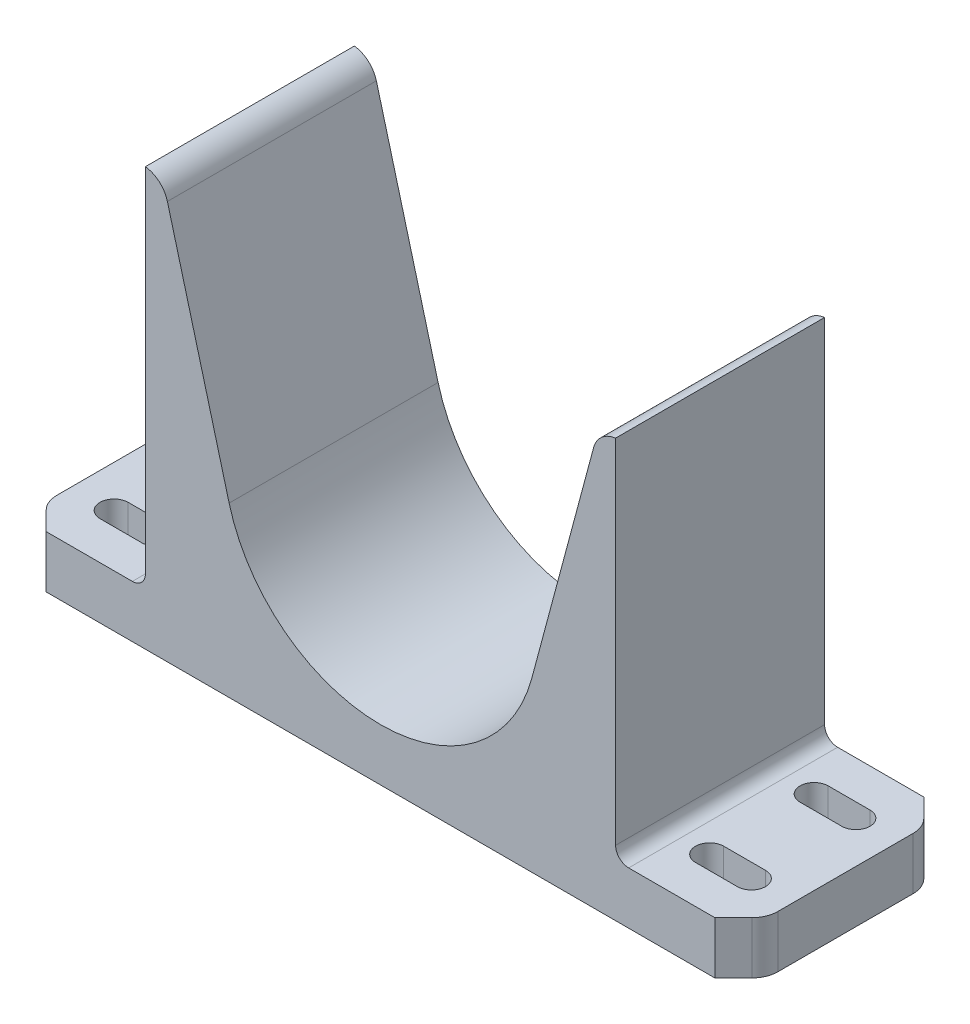
SolidWorks part; units mm, degrees
ref_plane "Front Plane" through (0, 0, 0) normal (0, 0, 1) x (1, 0, 0)
ref_plane "Top Plane" through (0, 0, 0) normal (0, 1, 0) x (1, 0, 0)
ref_plane "Right Plane" through (0, 0, 0) normal (1, 0, 0) x (0, 0, -1)
sketch "Sketch1" plane through (0, 0, 0) normal (0, 0, 1) x (1, 0, 0)
  line L0 (0, 0) -> (0, 198.0071) construction
  line L1 (-36.8018, 137.3461) -> (-53.0558, 198.0071)
  line L2 (-53.0558, 198.0071) -> (-57.15, 198.0071)
  line L3 (-57.15, 198.0071) -> (-57.15, 96.4071)
  line L4 (-57.15, 96.4071) -> (57.15, 96.4071)
  line L5 (57.15, 198.0071) -> (57.15, 96.4071)
  line L6 (53.0558, 198.0071) -> (57.15, 198.0071)
  line L7 (36.8018, 137.3461) -> (53.0558, 198.0071)
  arc A0 (36.8018, 137.3461) -> (-36.8018, 137.3461) centre (0, 147.2071) cw
  point P8 (0, 96.4071)
  point P19 (0, 109.1071)
  dimension "D2" = 38.1
  dimension "D1" = 30
  dimension "D3" = 88.9
  dimension "D4" = 12.7
  dimension "D5" = 114.3
extrude "Boss-Extrude1" add sketch "Sketch1" along normal blind 50.8
sketch "Sketch2" plane through (0, 96.4071, 0) normal (0, -1, 0) x (1, 0, 0)
  line L0 (-57.15, 25.4) -> (57.15, 25.4) construction
  line L1 (-57.15, 50.8) -> (-57.15, 0) construction
  line L2 (57.15, 50.8) -> (57.15, 0) construction
  line L3 (0, 50.8) -> (0, 0) construction
  line L4 (-57.15, 50.8) -> (57.15, 50.8) construction
  line L5 (-72.39, 0) -> (-72.39, 50.8) construction
  line L6 (-57.15, 0) -> (-87.63, 0)
  line L7 (-57.15, 0) -> (-57.15, 50.8)
  line L8 (-57.15, 50.8) -> (-87.63, 50.8)
  line L9 (-87.63, 0) -> (-87.63, 50.8)
  line L10 (-77.47, 12.7) -> (-67.31, 12.7) construction
  line L11 (-77.47, 16.129) -> (-67.31, 16.129)
  line L12 (-77.47, 9.271) -> (-67.31, 9.271)
  line L13 (-77.47, 38.1) -> (-67.31, 38.1) construction
  line L14 (-77.47, 34.671) -> (-67.31, 34.671)
  line L15 (-77.47, 41.529) -> (-67.31, 41.529)
  line L16 (87.63, 0) -> (87.63, 50.8)
  line L17 (57.15, 50.8) -> (87.63, 50.8)
  line L18 (57.15, 0) -> (57.15, 50.8)
  line L19 (57.15, 0) -> (87.63, 0)
  line L20 (77.47, 38.1) -> (67.31, 38.1) construction
  line L21 (77.47, 34.671) -> (67.31, 34.671)
  line L22 (77.47, 41.529) -> (67.31, 41.529)
  line L23 (72.39, 0) -> (72.39, 50.8) construction
  line L24 (77.47, 12.7) -> (67.31, 12.7) construction
  line L25 (77.47, 16.129) -> (67.31, 16.129)
  line L26 (77.47, 9.271) -> (67.31, 9.271)
  arc A0 (-77.47, 16.129) -> (-77.47, 9.271) centre (-77.47, 12.7) ccw
  arc A1 (-67.31, 9.271) -> (-67.31, 16.129) centre (-67.31, 12.7) ccw
  arc A2 (-77.47, 34.671) -> (-77.47, 41.529) centre (-77.47, 38.1) cw
  arc A3 (-67.31, 41.529) -> (-67.31, 34.671) centre (-67.31, 38.1) cw
  arc A4 (77.47, 34.671) -> (77.47, 41.529) centre (77.47, 38.1) ccw
  arc A5 (67.31, 41.529) -> (67.31, 34.671) centre (67.31, 38.1) ccw
  arc A6 (77.47, 16.129) -> (77.47, 9.271) centre (77.47, 12.7) cw
  arc A7 (67.31, 9.271) -> (67.31, 16.129) centre (67.31, 12.7) cw
  point P20 (-72.39, 12.7)
  point P27 (-72.39, 38.1)
  point P38 (72.39, 38.1)
  point P47 (72.39, 12.7)
  dimension "D1" = 30.48
  dimension "D2" = 6.858
  dimension "D3" = 10.16
  dimension "D4" = 25.4
extrude "Boss-Extrude2" add sketch "Sketch2" against normal blind 12.7
fillet "Fillet1" radius 3.175 2 edges at (-57.15, 109.1071, 25.4) (57.15, 109.1071, 25.4)
chamfer "Chamfer1" distance 6.35 angle 45 4 edges at (87.63, 102.7571, 50.8) (87.63, 102.7571, 0) (-87.63, 102.7571, 0) (-87.63, 102.7571, 50.8)
fillet "Fillet2" radius 6.35 4 edges at (87.63, 102.7571, 44.45) (87.63, 102.7571, 6.35) (-87.63, 102.7571, 44.45) (-87.63, 102.7571, 6.35)
fillet "Fillet3" radius 6.35 2 edges at (53.0558, 198.0071, 25.4) (-53.0558, 198.0071, 25.4)
